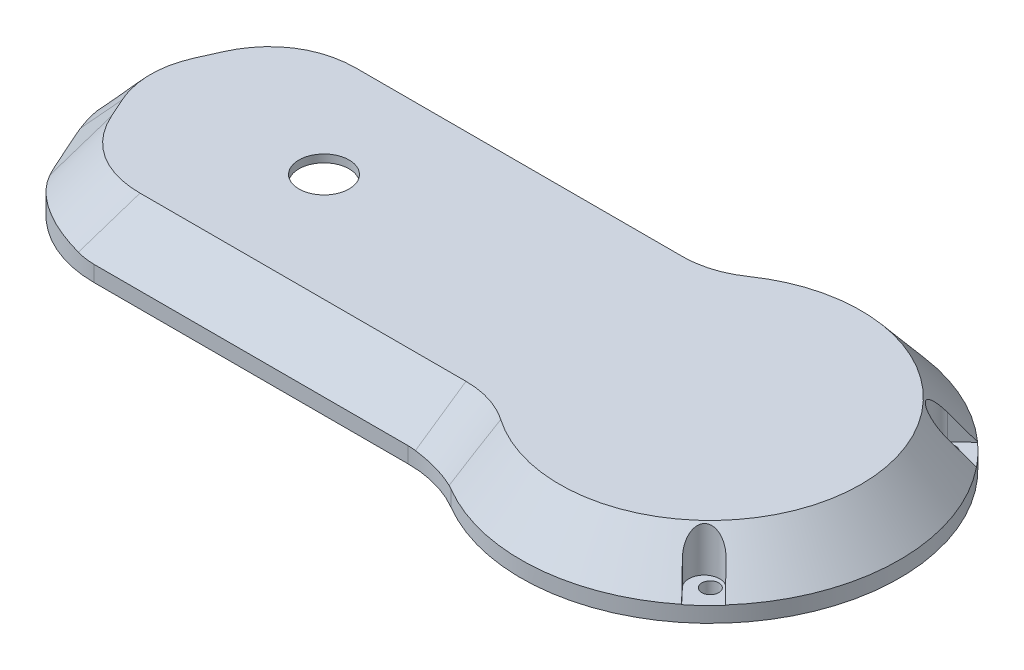
SolidWorks part; units mm, degrees
ref_plane "Front Plane" through (0, 0, 0) normal (0, 0, 1) x (1, 0, 0)
ref_plane "Top Plane" through (0, 0, 0) normal (0, 1, 0) x (1, 0, 0)
ref_plane "Right Plane" through (0, 0, 0) normal (1, 0, 0) x (0, 0, -1)
sketch "Sketch1" plane through (0, 0, 0) normal (0, 1, 0) x (1, 0, 0)
  line L0 (-25.7092, 18.7983) -> (-25.7092, -19.2017) construction
  line L1 (-25.7092, 18.7983) -> (-17.2092, 18.7983) construction
  line L2 (-17.2092, 18.7983) -> (-17.2092, -19.2017) construction
  line L3 (-17.2092, -19.2017) -> (-25.7092, -19.2017) construction
  line L4 (-25.7092, -0.2017) -> (-17.2092, 18.7983)
  line L5 (-25.7092, -0.2017) -> (-17.2092, -19.2017)
  line L6 (-25.7092, -0.2017) -> (53.2908, -0.2017) construction
  line L7 (-17.2092, 18.7983) -> (37.8231, 18.7983)
  line L8 (-17.2092, -19.2017) -> (13.7135, -19.2017)
  line L10 (13.7135, -19.2017) -> (37.8231, -19.2017)
  arc A0 (37.8231, -19.2017) -> (37.8231, 18.7983) centre (53.2908, -0.2017) ccw
  dimension "D4" = 49
  dimension "D1" = 38
  dimension "D2" = 8.5
  dimension "D3" = 79
extrude "Boss-Extrude1" add sketch "Sketch1" along normal blind 8
sketch "Sketch2" plane through (0, 8, 0) normal (0, 1, 0) x (1, 0, 0)
  line L0 (-20.2317, -0.2017) -> (-13.9685, 13.7983)
  line L1 (-13.9685, 13.7983) -> (39.7169, 13.7983)
  line L3 (39.7169, -14.2017) -> (-13.9685, -14.2017)
  line L4 (-13.9685, -14.2017) -> (-20.2317, -0.2017)
  line L5 (-17.2092, 18.7983) -> (-25.7092, -0.2017) construction
  line L6 (-25.7092, -0.2017) -> (-17.2092, -19.2017) construction
  line L7 (37.8231, 18.7983) -> (-17.2092, 18.7983) construction
  line L8 (-17.2092, -19.2017) -> (37.8231, -19.2017) construction
  arc A0 (39.7169, -14.2017) -> (39.7169, 13.7983) centre (53.2908, -0.2017) ccw
  dimension "D1" = 39
  dimension "D2" = 5
  dimension "D3" = 5
  dimension "D4" = 5
  dimension "D5" = 5
extrude "Cut-Extrude1" cut sketch "Sketch2" against normal blind 10 draft 40 flip side to cut
fillet "Fillet1" radius 15 10 edges at (-17.2092, 1.0206, -18.7983) (-15.5889, 5.0206, -16.2983) (37.8231, 1.0206, -18.7983) (37.8231, 1.0206, 19.2017) (-17.2092, 1.0206, 19.2017) (-15.5889, 5.0206, 16.7017) (-22.9705, 5.0206, 0.2017) (-25.7092, 1.0206, 0.2017)
sketch "Sketch3" plane through (0, 0, 0) normal (0, -1, 0) x (1, 0, 0)
  line L0 (53.2908, 0.2017) -> (3.2908, 0.2017) construction
  line L1 (3.2908, 0.2017) -> (-21.7092, 0.2017) construction
  line L2 (68.6208, 15.5318) -> (53.2908, 0.2017) construction
  line L3 (53.2908, 0.2017) -> (68.6208, -15.1284) construction
  line L4 (68.6208, -15.1284) -> (68.6208, 15.5318) construction
  circle A0 centre (53.2908, 0.2017) radius 21.68 construction
  circle A1 centre (-21.7092, 0.2017) radius 1.1
  circle A2 centre (68.6208, 15.5318) radius 1.1
  circle A3 centre (68.6208, -15.1284) radius 1.1
  dimension "D1" = 43.36
  dimension "D4" = 2.2
  dimension "D6" = 2.2
  dimension "D7" = 2.2
  dimension "D2" = 50
  dimension "D3" = 25
  dimension "D5" = 90
extrude "Cut-Extrude2" cut sketch "Sketch3" against normal blind 43
sketch "Sketch4" plane through (0, 0, 0) normal (0, -1, 0) x (1, 0, 0)
  line L0 (53.2908, 0.2017) -> (3.2908, 0.2017) construction
  line L2 (3.2908, 14.2017) -> (53.2908, 14.2017)
  line L4 (3.2908, -13.7983) -> (53.2908, -13.7983)
  arc A0 (53.2908, -13.7983) -> (53.2908, 14.2017) centre (53.2908, 0.2017) ccw
  arc A1 (3.2908, 14.2017) -> (3.2908, -13.7983) centre (3.2908, 0.2017) ccw
  dimension "D2" = 28
  dimension "D3" = 28
  dimension "D1" = 50
extrude "Cut-Extrude3" cut sketch "Sketch4" against normal blind 7
sketch "Sketch5" plane through (0, 7, 0) normal (0, -1, 0) x (1, 0, 0)
  circle A0 centre (3.2908, 0.2017) radius 3.25
  dimension "D1" = 6.5
extrude "Cut-Extrude4" cut sketch "Sketch5" against normal blind 6.5
sketch "Sketch6" plane through (0, 8, 0) normal (0, 1, 0) x (1, 0, 0)
  line L0 (69.0091, 14.73) -> (53.2908, -0.2017) construction
  line L1 (53.2908, -0.2017) -> (68.2225, -15.92) construction
  line L2 (67.6316, 16.1801) -> (70.4845, 18.8902)
  line L3 (70.4845, 18.8902) -> (73.6836, 16.412)
  line L4 (73.6836, 16.412) -> (70.3865, 13.28)
  line L5 (66.7725, -17.2975) -> (71.3629, -22.1297)
  line L6 (71.3629, -22.1297) -> (73.0042, -18.0497)
  line L7 (73.0042, -18.0497) -> (69.6726, -14.5426)
  line L13 (-21.7092, 1.7983) -> (-27.8634, 1.7983)
  line L15 (-21.7092, -2.2017) -> (-27.8634, -2.2017)
  line L16 (-27.8634, 1.7983) -> (-27.8634, -2.2017)
  circle A1 centre (53.2908, -0.2017) radius 21.68 construction
  arc A2 (67.6316, 16.1801) -> (70.3865, 13.28) centre (69.0091, 14.73) ccw
  arc A3 (69.6726, -14.5426) -> (66.7725, -17.2975) centre (68.2225, -15.92) ccw
  arc A4 (-21.7092, -2.2017) -> (-21.7092, 1.7983) centre (-21.7092, -0.2017) ccw
  dimension "D1" = 4
  dimension "D2" = 4
  dimension "D3" = 4
  dimension "D4" = 43.36
extrude "Cut-Extrude5" cut sketch "Sketch6" against normal blind 6
